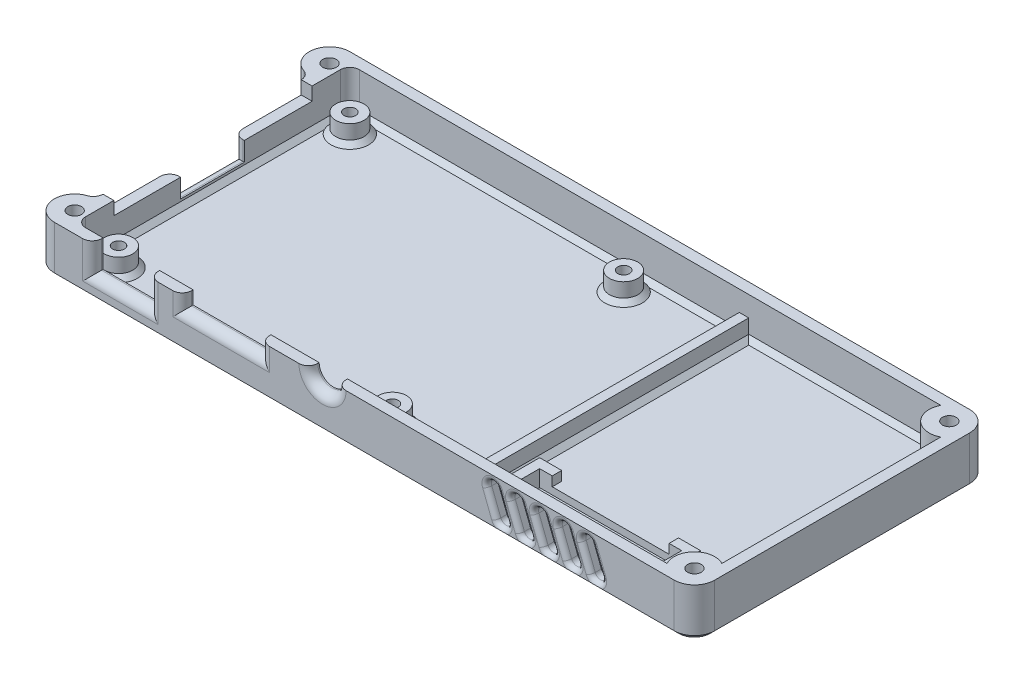
SolidWorks part; units mm, degrees
ref_plane "Front Plane" through (0, 0, 0) normal (0, 0, 1) x (1, 0, 0)
ref_plane "Top Plane" through (0, 0, 0) normal (0, 1, 0) x (1, 0, 0)
ref_plane "Right Plane" through (0, 0, 0) normal (1, 0, 0) x (0, 0, -1)
sketch "Sketch1" plane through (0, 0, 0) normal (0, 1, 0) x (1, 0, 0)
  line L0 (-71.5618, 3.106) -> (57.4382, 3.106) construction
  line L1 (-71.5618, 31.106) -> (57.4382, 31.106)
  line L2 (-71.5618, 31.106) -> (-71.5618, -24.894)
  line L3 (-71.5618, -24.894) -> (57.4382, -24.894)
  line L4 (57.4382, 31.106) -> (57.4382, -24.894)
  line L5 (-60.6618, -24.894) -> (-60.6618, -31.6828) construction
  line L6 (-68.0618, 27.606) -> (-10.0618, 27.606)
  line L7 (-68.0618, 27.606) -> (-68.0618, -21.394)
  line L8 (-68.0618, -21.394) -> (-10.0618, -21.394)
  line L9 (-10.0618, 27.606) -> (-10.0618, -21.394)
  line L10 (-39.5618, -24.894) -> (-39.5618, -31.6828) construction
  line L11 (-18.0618, -24.894) -> (-18.0618, -31.6828) construction
  line L12 (-65.4118, -26.5648) -> (-55.9118, -26.5648) construction
  line L13 (-48.0618, -26.5648) -> (-31.0618, -26.5648) construction
  line L14 (-22.0618, -26.5648) -> (-14.0618, -26.5648) construction
  line L15 (-72.5618, 9.606) -> (-72.5618, -3.394) construction
  line L16 (-71.5618, 3.106) -> (-72.5618, 3.106) construction
  dimension "D1" = 129
  dimension "D2" = 56
  dimension "D3" = 49
  dimension "D4" = 58
  dimension "D5" = 3.5
  dimension "D6" = 3.5
  dimension "D7" = 10.9
  dimension "D8" = 32
  dimension "D9" = 53.5
  dimension "D10" = 2
  dimension "D11" = 13
  dimension "D12" = 9.5
  dimension "D13" = 17
  dimension "D14" = 8
sketch "Sketch3" plane through (0, 0, 0) normal (0, 1, 0) x (1, 0, 0)
  line L4 (60.7382, 34.406) -> (-74.8618, 34.406)
  line L5 (-74.8618, 34.406) -> (-74.8618, -28.194)
  line L6 (-74.8618, -28.194) -> (60.7382, -28.194)
  line L7 (60.7382, -28.194) -> (60.7382, 34.406)
  line L8 (58.4382, 32.106) -> (-72.5618, 32.106)
  line L9 (58.4382, -25.894) -> (58.4382, 32.106)
  line L10 (-72.5618, -25.894) -> (58.4382, -25.894)
  line L11 (-72.5618, 32.106) -> (-72.5618, -25.894)
  line L12 (58.4382, 32.106) -> (-72.5618, 32.106)
  line L13 (58.4382, -25.894) -> (58.4382, 32.106)
  line L14 (-72.5618, -25.894) -> (58.4382, -25.894)
  line L15 (-72.5618, 32.106) -> (-72.5618, -25.894)
  line L16 (-7.0618, 3.106) -> (-7.0618, 34.406) construction
  line L17 (-71.5618, 3.106) -> (57.4382, 3.106) construction
  line L20 (-74.8618, 3.106) -> (52.7382, 3.106) construction
  line L25 (60.7382, -28.194) -> (60.7382, 34.406) construction
  line L26 (58.4382, -25.894) -> (58.4382, 32.106) construction
  dimension "D1" = 1
  dimension "D2" = 2.3
extrude "Boss-Extrude1" add sketch "Sketch3" along normal blind 10.3
sketch "Sketch5" plane through (0, 0, 0) normal (0, 1, 0) x (1, 0, 0)
  line L1 (-72.5618, 32.106) -> (58.4382, 32.106)
  line L2 (-72.5618, 32.106) -> (-72.5618, -25.894)
  line L3 (-72.5618, -25.894) -> (58.4382, -25.894)
  line L4 (58.4382, 32.106) -> (58.4382, -25.894)
extrude "Boss-Extrude2" add sketch "Sketch5" along normal blind 2
sketch "Sketch6" plane through (0, 2, 0) normal (0, 1, 0) x (1, 0, 0)
  circle A0 centre (-68.0618, 27.606) radius 3
  circle A1 centre (-68.0618, -21.394) radius 3
  circle A2 centre (-10.0618, -21.394) radius 3
  circle A3 centre (-10.0618, 27.606) radius 3
extrude "Boss-Extrude3" add sketch "Sketch6" along normal blind 4
hole_wizard "Ø2.5 (2.5) Diameter Hole1" positions "Sketch8" profile "Sketch9" hole size "Ø2.5" standard "ANSI Metric"
sketch "Sketch8" plane through (0, 6, 0) normal (0, 1, 0) x (1, 0, 0)
  point P0 (-68.0618, 27.606)
  point P3 (-10.0618, 27.606)
  point P6 (-10.0618, -21.394)
  point P9 (-68.0618, -21.394)
sketch "Sketch9" plane through (-68.0618, 6, -27.606) normal (1, 0, 0) x (0, 0, 1)
  line L0 (0, 0) -> (0, 8.7511)
  line L1 (0, 8.7511) -> (1.25, 8)
  line L2 (1.25, 8) -> (1.25, 0)
  line L5 (1.25, 0) -> (0, 0)
  line L10 (0, 8.7511) -> (-1.25, 8) construction
  line L11 (0, -6.35) -> (0, 107.95) construction
  dimension "Hole Dia." = 2.5
  dimension "Hole Depth" = 8
  dimension "Drill Angle" = 118
sketch "Sketch10" plane through (0, 2, 0) normal (0, 1, 0) x (1, 0, 0)
  line L0 (58.4382, 32.106) -> (-72.5618, 32.106) construction
  line L1 (9.9382, 32.106) -> (11.9382, 32.106)
  line L2 (9.9382, 32.106) -> (9.9382, -25.894)
  line L3 (9.9382, -25.894) -> (11.9382, -25.894)
  line L4 (11.9382, 32.106) -> (11.9382, -25.894)
  line L5 (-72.5618, -25.894) -> (58.4382, -25.894) construction
  line L6 (-10.0618, 27.606) -> (-10.0618, -21.394) construction
  dimension "D1" = 2
  dimension "D2" = 20
extrude "Boss-Extrude4" add sketch "Sketch10" along normal blind 4
sketch "Sketch11" plane through (0, 0, 28.194) normal (0, 0, 1) x (1, 0, 0)
  line L0 (-74.8618, 10.3) -> (-74.8618, 0) construction
  line L1 (-66.8618, 10.3) -> (-54.8618, 10.3)
  line L2 (-66.8618, 10.3) -> (-66.8618, 4.5)
  line L3 (-66.8618, 4.5) -> (-54.8618, 4.5)
  line L4 (-54.8618, 10.3) -> (-54.8618, 4.5)
  line L5 (-74.8618, 0) -> (60.7382, 0) construction
  line L6 (-60.8618, 10.3) -> (-60.6618, 0) construction
  line L7 (-65.4118, 0) -> (-55.9118, 0) construction
  line L9 (-47.778, 10.3) -> (-31.278, 10.3)
  line L10 (-47.778, 10.3) -> (-47.778, 7.5)
  line L11 (-47.778, 7.5) -> (-31.278, 7.5)
  line L12 (-31.278, 10.3) -> (-31.278, 7.5)
  line L13 (-68.0618, 0) -> (-10.0618, 0) construction
  line L14 (-39.5618, 0) -> (-39.528, 10.3) construction
  line L15 (-48.0618, 0) -> (-31.0618, 0) construction
  line L16 (-18.0618, 0) -> (-18.0618, 10.3) construction
  line L17 (-22.0618, 0) -> (-14.0618, 0) construction
  line L18 (-74.8618, 10.3) -> (60.7382, 10.3) construction
  circle A0 centre (-18.0618, 10.3) radius 3
  dimension "D5" = 6
  dimension "D1" = 4.5
  dimension "D2" = 12
  dimension "D3" = 7.5
  dimension "D4" = 16.5
  dimension "D6" = 8
extrude "Cut-Extrude1" cut sketch "Sketch11" against normal up to next
sketch "Sketch12" plane through (-74.8618, 0, 0) normal (-1, 0, 0) x (0, 0, 1)
  line L0 (-3.106, 0) -> (-3.106, 10.3) construction
  line L1 (-27.606, 0) -> (21.394, 0) construction
  line L2 (-34.406, 10.3) -> (28.194, 10.3) construction
  line L3 (17.894, 10.3) -> (17.894, 7.5)
  line L4 (-9.7329, 10.3) -> (3.7671, 10.3)
  line L5 (-9.7329, 10.3) -> (-9.7329, 3.5)
  line L6 (-9.7329, 3.5) -> (3.7671, 3.5)
  line L7 (3.7671, 10.3) -> (3.7671, 3.5)
  line L8 (-24.106, 10.3) -> (17.894, 10.3)
  line L9 (-24.106, 10.3) -> (-24.106, 7.5)
  line L10 (-24.106, 7.5) -> (17.894, 7.5)
  dimension "D1" = 13.5
  dimension "D2" = 3.5
  dimension "D3" = 7.5
extrude "Cut-Extrude2" cut sketch "Sketch12" against normal up to next contours L10 L3 L8 L9 | L7 L6 L5 L4
fillet "Fillet6" radius 2 1 edges at (58.4382, 6.15, -32.106)
fillet "Fillet8" radius 2 2 edges at (-72.5618, 6.15, 25.894) (-72.5618, 6.15, -32.106)
chamfer "Chamfer1" distance 1 angle 45 4 edges at (-68.0618, 2, 24.394) (-10.0618, 2, 24.394) (-10.0618, 2, -24.606) (-68.0618, 2, -24.606)
fillet "Fillet9" radius 2 9 edges at (-74.8618, 5.5, -9.7329) (-74.8618, 3.5, -2.9829) (-74.8618, 5.5, 3.7671) (-18.0618, 7.3, 28.194) (-31.278, 8.9, 28.194) (-47.778, 8.9, 28.194) (-39.528, 7.5, 28.194) (-54.8618, 7.4, 28.194) (-60.8618, 4.5, 28.194)
sketch "Sketch17" plane through (0, 0, 0) normal (0, 1, 0) x (1, 0, 0)
  line L0 (-74.8618, 34.406) -> (-74.8618, 24.106) construction
  line L1 (-74.8618, 34.406) -> (-74.8618, 25.806)
  line L2 (-74.8618, 25.806) -> (-74.659, 25.9406)
  line L3 (-74.8618, -19.594) -> (-74.8618, -28.194)
  line L4 (-74.8618, -28.194) -> (-74.659, -28.0594)
  arc A0 (-74.8618, -19.594) -> (-74.8618, -28.194) centre (-74.8618, -23.894) ccw
  arc A1 (-74.8618, 34.406) -> (-74.8618, 25.806) centre (-74.8618, 30.106) ccw
extrude "Boss-Extrude6" add sketch "Sketch17" along normal up to vertex (10.3 mm away) contours L1 A1 | L3 A0 region at (-76.6867, 0, -30.106) region at (-76.6867, 0, 23.894) up to point (-74.8618, 10.3, 28.194)
hole_wizard "Ø2.9 (2.9) Diameter Hole2" positions "Sketch19" profile "Sketch18" hole size "Ø2.9" standard "ANSI Metric" end condition up to next
sketch "Sketch19" plane through (0, 10.3, 0) normal (0, 1, 0) x (1, 0, 0)
  point P0 (-74.8618, 30.106)
sketch "Sketch18" plane through (-74.8618, 10.3, -30.106) normal (1, 0, 0) x (0, 0, 1)
  line L0 (0, 0) -> (0, 10.3)
  line L1 (0, 10.3) -> (1.45, 10.3)
  line L2 (1.45, 10.3) -> (1.45, 0)
  line L5 (1.45, 0) -> (0, 0)
  line L11 (0, -6.35) -> (0, 107.95) construction
  dimension "Thru Hole Dia." = 2.9
  dimension "Thru Hole Depth" = 10.3
hole_wizard "Ø2.9 (2.9) Diameter Hole1" positions "Sketch21" profile "Sketch20" hole size "Ø2.9" standard "ANSI Metric" end condition up to next
sketch "Sketch21" plane through (0, 10.3, 0) normal (0, 1, 0) x (1, 0, 0)
  point P0 (-74.8618, -23.894)
sketch "Sketch20" plane through (-74.8618, 10.3, 23.894) normal (1, 0, 0) x (0, 0, 1)
  line L0 (0, 0) -> (0, 10.3)
  line L1 (0, 10.3) -> (1.45, 10.3)
  line L2 (1.45, 10.3) -> (1.45, 0)
  line L5 (1.45, 0) -> (0, 0)
  line L11 (0, -6.35) -> (0, 107.95) construction
  dimension "Thru Hole Dia." = 2.9
  dimension "Thru Hole Depth" = 10.3
sketch "Sketch24" plane through (0, 2, 0) normal (0, 1, 0) x (1, 0, 0)
  line L0 (11.9382, 3.106) -> (61.5789, 3.106) construction
  line L1 (11.9382, -25.894) -> (11.9382, 32.106) construction
  line L2 (60.7382, -28.194) -> (60.7382, 34.406) construction
  circle A0 centre (56.4382, -23.894) radius 4.3
  circle A1 centre (56.4382, 30.106) radius 4.3
  dimension "D1" = 4.3
extrude "Boss-Extrude7" add sketch "Sketch24" along normal up to surface (8.3 mm away) up to face at (-74.8618, 10.3, -28.656)
hole_wizard "Ø2.9 (2.9) Diameter Hole5" positions "Sketch31" profile "Sketch30" hole size "Ø2.9" standard "ANSI Metric" end condition up to next
sketch "Sketch31" plane through (0, 10.3, 0) normal (0, 1, 0) x (1, 0, 0)
  point P0 (56.4382, -23.894)
sketch "Sketch30" plane through (56.4382, 10.3, 23.894) normal (1, 0, 0) x (0, 0, 1)
  line L0 (0, 0) -> (0, 10.3)
  line L1 (0, 10.3) -> (1.45, 10.3)
  line L2 (1.45, 10.3) -> (1.45, 0)
  line L5 (1.45, 0) -> (0, 0)
  line L11 (0, -6.35) -> (0, 107.95) construction
  dimension "Thru Hole Dia." = 2.9
  dimension "Thru Hole Depth" = 10.3
hole_wizard "Ø2.9 (2.9) Diameter Hole4" positions "Sketch28" profile "Sketch27" hole size "Ø2.9" standard "ANSI Metric" end condition up to next
sketch "Sketch28" plane through (0, 10.3, 0) normal (0, 1, 0) x (1, 0, 0)
  point P0 (56.4382, 30.106)
sketch "Sketch27" plane through (56.4382, 10.3, -30.106) normal (1, 0, 0) x (0, 0, 1)
  line L0 (0, 0) -> (0, 10.3)
  line L1 (0, 10.3) -> (1.45, 10.3)
  line L2 (1.45, 10.3) -> (1.45, 0)
  line L5 (1.45, 0) -> (0, 0)
  line L11 (0, -6.35) -> (0, 107.95) construction
  dimension "Thru Hole Dia." = 2.9
  dimension "Thru Hole Depth" = 10.3
fillet "Fillet10" radius 4.3 1 edges at (60.7382, 5.15, -34.406)
fillet "Fillet18" radius 2 2 edges at (-74.8618, 5.15, 19.594) (-74.8618, 5.15, -25.806)
chamfer "Chamfer3" distance 1 angle 45 9 edges at (59.4788, 0, -33.1466) (-9.2118, 0, -34.406) (60.7382, 0, -0.956) (-79.1058, 0, -30.7975) (-75.2385, 0, -25.3002) (-74.8618, 0, -3.106) (-75.2385, 0, 19.0883) (-79.1058, 0, 24.5855) (-7.0618, 0, 28.194)
fillet "Fillet19" radius 2 1 edges at (-66.8618, 6.4, 28.194)
fillet "Fillet20" radius 4.3 1 edges at (60.7382, 5.65, 28.194)
chamfer "Chamfer5" distance 1 angle 45 8 edges at (-72.5618, 2, -3.106) (-71.976, 2, 25.3082) (-71.976, 2, -31.5202) (-30.3118, 2, 25.894) (-30.3118, 2, -32.106) (9.9382, 2, -3.106) (11.9382, 2, -3.106) (32.2849, 2, -32.106)
chamfer "Chamfer6" distance 1 angle 45 1 edges at (58.4382, 2, -3.106)
sketch "Sketch32" plane through (0, 2, 0) normal (0, 1, 0) x (1, 0, 0)
  line L0 (12.9382, -25.894) -> (52.6317, -25.894) construction
  line L1 (15.4382, -15.694) -> (45.5382, -15.694)
  line L2 (15.4382, -15.694) -> (15.4382, -25.894)
  line L3 (15.4382, -25.894) -> (45.5382, -25.894)
  line L4 (45.5382, -15.694) -> (45.5382, -25.894)
  line L5 (-72.5618, -23.894) -> (-72.5618, 30.106) construction
  dimension "D1" = 10.2
  dimension "D2" = 30.1
  dimension "D3" = 88
extrude "Cut-Extrude4" cut sketch "Sketch32" against normal blind 1.5
sketch "Sketch33" plane through (0, 2, 0) normal (0, 1, 0) x (1, 0, 0)
  line L0 (15.4382, -15.694) -> (15.4382, -25.894)
  line L2 (15.4382, -25.894) -> (13.4382, -25.894)
  line L3 (12.9382, -25.894) -> (15.4382, -25.894) construction
  line L4 (47.5382, -13.694) -> (47.5382, -20.8822)
  line L5 (47.5382, -20.8822) -> (45.5382, -20.8822)
  line L6 (45.5382, -25.894) -> (45.5382, -20.7012) construction
  line L7 (45.5382, -20.8822) -> (45.5382, -15.694)
  line L8 (30.4882, -15.694) -> (30.4882, -23.4127) construction
  line L9 (45.5382, -15.694) -> (15.4382, -15.694) construction
  line L10 (18.1083, -13.694) -> (18.1083, -15.694)
  line L11 (42.8681, -13.694) -> (42.8681, -15.694)
  line L12 (13.4382, -13.694) -> (13.4382, -27.894)
  line L13 (13.4382, -27.894) -> (47.5382, -27.894)
  line L14 (47.5382, -27.894) -> (47.5382, -13.694)
  line L15 (47.5382, -13.694) -> (13.4382, -13.694)
  line L16 (13.4382, -13.694) -> (13.4382, -25.894)
  line L17 (45.5382, -15.694) -> (42.8681, -15.694)
  line L19 (47.5382, -13.694) -> (42.8681, -13.694)
  line L20 (18.1083, -13.694) -> (13.4382, -13.694)
  line L21 (18.1083, -15.694) -> (15.4382, -15.694)
  dimension "D1" = 2
extrude "Boss-Extrude9" add sketch "Sketch33" along normal blind 2
sketch "Sketch34" plane through (0, 0, 28.194) normal (0, 0, 1) x (1, 0, 0)
  line L0 (17.9748, 7.7443) -> (19.8911, 2.8029) construction
  line L1 (19.1402, 8.1963) -> (21.0565, 3.2549)
  line L2 (16.8093, 7.2924) -> (18.7256, 2.3509)
  line L3 (22.9748, 7.7443) -> (24.8911, 2.8029) construction
  line L4 (24.1402, 8.1963) -> (26.0565, 3.2549)
  line L5 (21.8093, 7.2924) -> (23.7256, 2.3509)
  line L6 (27.9748, 7.7443) -> (29.8911, 2.8029) construction
  line L7 (29.1402, 8.1963) -> (31.0565, 3.2549)
  line L8 (26.8093, 7.2924) -> (28.7256, 2.3509)
  line L9 (32.9748, 7.7443) -> (34.8911, 2.8029) construction
  line L10 (34.1402, 8.1963) -> (36.0565, 3.2549)
  line L11 (31.8093, 7.2924) -> (33.7256, 2.3509)
  line L12 (37.9748, 7.7443) -> (39.8911, 2.8029) construction
  line L13 (39.1402, 8.1963) -> (41.0565, 3.2549)
  line L14 (36.8093, 7.2924) -> (38.7256, 2.3509)
  arc A0 (19.1402, 8.1963) -> (16.8093, 7.2924) centre (17.9748, 7.7443) ccw
  arc A1 (18.7256, 2.3509) -> (21.0565, 3.2549) centre (19.8911, 2.8029) ccw
  arc A2 (24.1402, 8.1963) -> (21.8093, 7.2924) centre (22.9748, 7.7443) ccw
  arc A3 (23.7256, 2.3509) -> (26.0565, 3.2549) centre (24.8911, 2.8029) ccw
  arc A4 (29.1402, 8.1963) -> (26.8093, 7.2924) centre (27.9748, 7.7443) ccw
  arc A5 (28.7256, 2.3509) -> (31.0565, 3.2549) centre (29.8911, 2.8029) ccw
  arc A6 (34.1402, 8.1963) -> (31.8093, 7.2924) centre (32.9748, 7.7443) ccw
  arc A7 (33.7256, 2.3509) -> (36.0565, 3.2549) centre (34.8911, 2.8029) ccw
  arc A8 (39.1402, 8.1963) -> (36.8093, 7.2924) centre (37.9748, 7.7443) ccw
  arc A9 (38.7256, 2.3509) -> (41.0565, 3.2549) centre (39.8911, 2.8029) ccw
  point P2 (18.9329, 5.2736)
  point P9 (23.9329, 5.2736)
  point P16 (28.9329, 5.2736)
  point P23 (33.9329, 5.2736)
  point P30 (38.9329, 5.2736)
extrude "Cut-Extrude5" cut sketch "Sketch34" against normal up to next
fillet "Fillet21" radius 1 20 edges at (37.5228, 8.9098, 28.194) (40.0983, 5.7256, 28.194) (40.343, 1.6375, 28.194) (32.5228, 8.9098, 28.194) (35.0983, 5.7256, 28.194) (35.343, 1.6375, 28.194) (27.5228, 8.9098, 28.194) (30.0983, 5.7256, 28.194) (30.343, 1.6375, 28.194) (22.5228, 8.9098, 28.194) (25.0983, 5.7256, 28.194) (25.343, 1.6375, 28.194) (17.5228, 8.9098, 28.194) (20.0983, 5.7256, 28.194) (20.343, 1.6375, 28.194) (37.7675, 4.8217, 28.194) (32.7675, 4.8217, 28.194) (27.7675, 4.8217, 28.194) (22.7675, 4.8217, 28.194) (17.7675, 4.8217, 28.194)
chamfer "Chamfer7" distance 1 angle 45 1 edges at (59.4788, 0, 26.9346)
